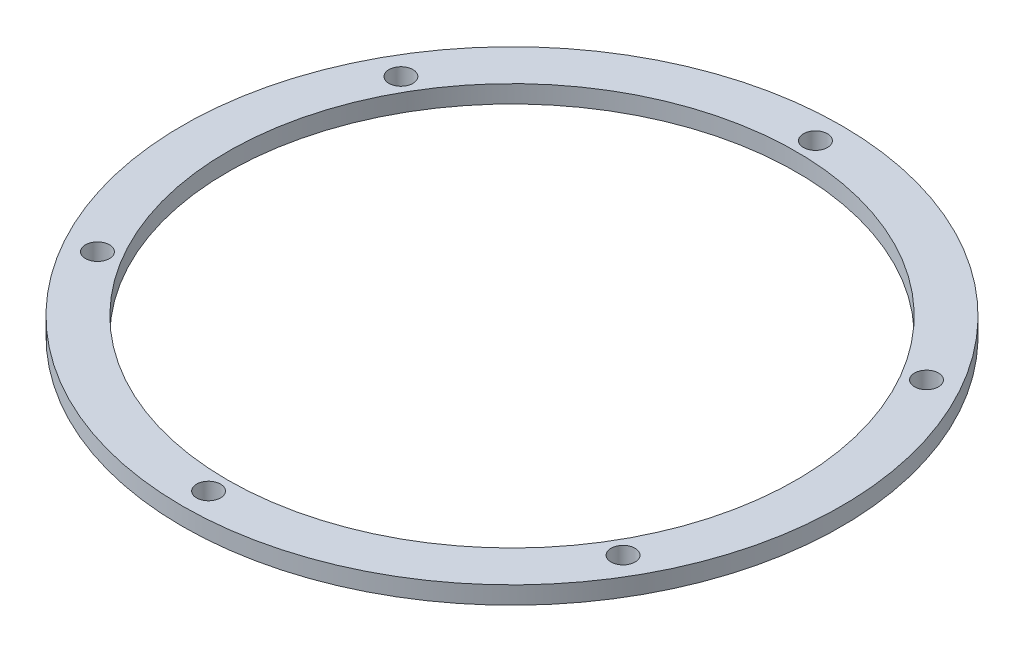
SolidWorks part; units mm, degrees
ref_plane "Front Plane" through (0, 0, 0) normal (0, 0, 1) x (1, 0, 0)
ref_plane "Top Plane" through (0, 0, 0) normal (0, 1, 0) x (1, 0, 0)
ref_plane "Right Plane" through (0, 0, 0) normal (1, 0, 0) x (0, 0, -1)
sketch "Sketch1" plane through (0, 0, 0) normal (0, 1, 0) x (1, 0, 0)
  circle A0 centre (0, 0) radius 51.181
  circle A1 centre (0, 0) radius 59.309
  dimension "D1" = 118.618
  dimension "D2" = 102.362
extrude "Boss-Extrude1" add sketch "Sketch1" along normal blind 3.175
sketch "Sketch2" plane through (0, 3.175, 0) normal (0, 1, 0) x (1, 0, 0)
  line L0 (0, 0) -> (0, 54.61) construction
  circle A0 centre (0, 0) radius 54.61 construction
  circle A1 centre (0, 54.61) radius 2.159
  dimension "D1" = 109.22
extrude "Cut-Extrude1" cut sketch "Sketch2" against normal up to next
pattern_circular "CirPattern1" count 6 over 360 about axis through (0, 3.175, 0) along (0, -1, 0) of "Cut-Extrude1" reverse direction yes
